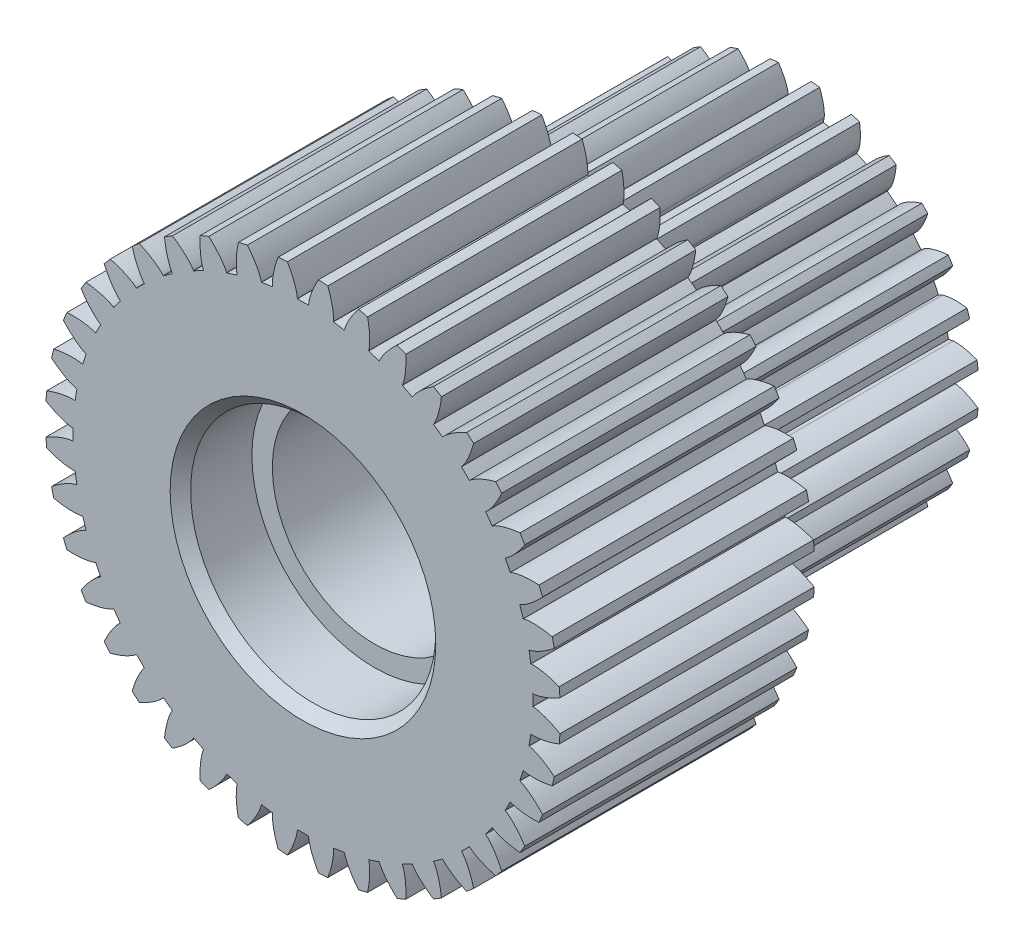
SolidWorks part; units mm, degrees
material "PLA"
ref_plane "Front Plane" through (0, 0, 0) normal (0, 0, 1) x (1, 0, 0)
ref_plane "Top Plane" through (0, 0, 0) normal (0, 1, 0) x (1, 0, 0)
ref_plane "Right Plane" through (0, 0, 0) normal (1, 0, 0) x (0, 0, -1)
sketch "Sketch1" plane through (0, 0, 0) normal (0, 0, 1) x (1, 0, 0)
  circle A0 centre (0, 0) radius 12.6
  dimension "D1" = 25.2
extrude "Boss-Extrude1" add sketch "Sketch1" along normal mid plane 12.446
sketch "Sketch2" plane through (0, 0, 0) normal (0, 0, 1) x (1, 0, 0)
  line L0 (0, 0) -> (11.9964, 0.2924) construction
  line L1 (0, 0) -> (12, 0) construction
  line L2 (0, 0) -> (11.9964, -0.2924) construction
  line L3 (11.2705, -0.2747) -> (11.2467, -0.2741)
  line L4 (11.273, 0.2747) -> (11.2467, 0.2741)
  circle A0 centre (0, 0) radius 12 construction
  circle A1 centre (0, 0) radius 11.2763 construction
  circle A2 centre (0, 0) radius 11.25
  circle A3 centre (0, 0) radius 12.6 construction
  circle A4 centre (0, 0) radius 12.6
  spline S0 degree 4 poles (11.273, 0.2747) (11.2768, 0.2749) (11.2876, 0.2755) (11.308, 0.2773) (11.3412, 0.2811) (11.3834, 0.2875) (11.4377, 0.2974) (11.5015, 0.311) (11.5713, 0.3282) (11.6468, 0.3492) (11.7218, 0.3723) (11.7963, 0.3972) (11.8701, 0.4237) (11.9591, 0.4578) (12.0652, 0.5015) (12.1882, 0.5566) (12.3264, 0.6239) (12.4657, 0.6975) (12.6016, 0.774) (12.7374, 0.8561) (12.8676, 0.9388) (13.0012, 1.0294) (13.1236, 1.1155) (13.2588, 1.2171) (13.3673, 1.3006) (13.5081, 1.4161) (13.5906, 1.486) (13.6863, 1.5697) (13.7283, 1.6078) (13.7543, 1.6313) knots 0 0 0 0 0 0.005377 0.015084 0.028532 0.04661 0.064855 0.092111 0.119476 0.146842 0.174209 0.201575 0.228941 0.256307 0.307035 0.361767 0.4165 0.471232 0.525964 0.580697 0.635429 0.690161 0.744894 0.799626 0.854358 0.909091 0.954545 1 1 1 1 1 construction
  spline S1 degree 4 poles (11.273, 0.2747) (11.2768, 0.2749) (11.2876, 0.2755) (11.308, 0.2773) (11.3412, 0.2811) (11.3834, 0.2875) (11.4377, 0.2974) (11.5015, 0.311) (11.5713, 0.3282) (11.6468, 0.3492) (11.7218, 0.3723) (11.7963, 0.3972) (11.8701, 0.4237) (11.9591, 0.4578) (12.0652, 0.5015) (12.1882, 0.5566) (12.3264, 0.6239) (12.4657, 0.6975) (12.6016, 0.774) (12.7374, 0.8561) (12.8676, 0.9388) (13.0012, 1.0294) (13.1236, 1.1155) (13.2588, 1.2171) (13.3673, 1.3006) (13.4776, 1.3911) (13.531, 1.4358) (13.5582, 1.4589) knots 0 0 0 0 0 0.005377 0.015084 0.028532 0.04661 0.064855 0.092111 0.119476 0.146842 0.174209 0.201575 0.228941 0.256307 0.307035 0.361767 0.4165 0.471232 0.525964 0.580697 0.635429 0.690161 0.744894 0.799626 0.854358 0.909091 0.909091 0.909091 0.909091 0.909091
  spline S2 degree 4 poles (11.2705, -0.2747) (11.2744, -0.2748) (11.2852, -0.2754) (11.3055, -0.2772) (11.3387, -0.2811) (11.3809, -0.2875) (11.4353, -0.2973) (11.499, -0.311) (11.5688, -0.3282) (11.6444, -0.3492) (11.7194, -0.3722) (11.7938, -0.3971) (11.8677, -0.4236) (11.9567, -0.4577) (12.0627, -0.5014) (12.1857, -0.5566) (12.3239, -0.6238) (12.4633, -0.6974) (12.5992, -0.774) (12.7349, -0.856) (12.8652, -0.9387) (12.9988, -1.0293) (13.1212, -1.1154) (13.2563, -1.217) (13.3648, -1.3005) (13.5056, -1.4161) (13.5881, -1.486) (13.6838, -1.5696) (13.7259, -1.6077) (13.7518, -1.6312) knots 0 0 0 0 0 0.005377 0.015084 0.028532 0.04661 0.064855 0.092111 0.119476 0.146842 0.174209 0.201575 0.228941 0.256307 0.307035 0.361767 0.4165 0.471232 0.525964 0.580697 0.635429 0.690161 0.744894 0.799626 0.854358 0.909091 0.954545 1 1 1 1 1 construction
  spline S3 degree 4 poles (11.2705, -0.2747) (11.2744, -0.2748) (11.2852, -0.2754) (11.3055, -0.2772) (11.3387, -0.2811) (11.3809, -0.2875) (11.4353, -0.2973) (11.499, -0.311) (11.5688, -0.3282) (11.6444, -0.3492) (11.7194, -0.3722) (11.7938, -0.3971) (11.8677, -0.4236) (11.9567, -0.4577) (12.0627, -0.5014) (12.1857, -0.5566) (12.3239, -0.6238) (12.4633, -0.6974) (12.5992, -0.774) (12.7349, -0.856) (12.8652, -0.9387) (12.9988, -1.0293) (13.1212, -1.1154) (13.2563, -1.217) (13.3648, -1.3005) (13.4751, -1.391) (13.5285, -1.4357) (13.5557, -1.4588) knots 0 0 0 0 0 0.005377 0.015084 0.028532 0.04661 0.064855 0.092111 0.119476 0.146842 0.174209 0.201575 0.228941 0.256307 0.307035 0.361767 0.4165 0.471232 0.525964 0.580697 0.635429 0.690161 0.744894 0.799626 0.854358 0.909091 0.909091 0.909091 0.909091 0.909091
  dimension "D1" = 24
  dimension "D2" = 22.5526
  dimension "D3" = 22.5
  dimension "D4" = 1.396
  dimension "D5" = 1.396
extrude "Cut-Extrude1" cut sketch "Sketch2" against normal through all both and the other way through all
pattern_circular "CirPattern2" count 40 over 360 about axis through (0, 0, 6.223) along (0, 0, -1) of "Cut-Extrude1"
sketch "Sketch3" plane through (0, 0, 6.223) normal (0, 0, 1) x (1, 0, 0)
  circle A0 centre (0, 0) radius 5
  dimension "D1" = 10
sketch "Sketch4" plane through (0, 0, -6.223) normal (0, 0, -1) x (-1, 0, 0)
  circle A0 centre (0, 0) radius 9
  dimension "D1" = 18
extrude "Boss-Extrude2" add sketch "Sketch4" along normal blind 11.6295
sketch "Sketch5" plane through (0, 0, -17.8525) normal (0, 0, -1) x (-1, 0, 0)
  line L0 (0, 0) -> (9, 0) construction
  line L1 (0, 0) -> (8.9924, 0.3707) construction
  line L2 (0, 0) -> (8.9924, -0.3707) construction
  line L3 (7.8649, 0.3242) -> (7.6435, 0.3151)
  line L4 (7.8649, -0.3242) -> (7.6435, -0.3151)
  circle A0 centre (0, 0) radius 7.8934 construction
  circle A1 centre (0, 0) radius 7.65
  arc A2 (8.9642, -0.8024) -> (8.9642, 0.8024) centre (0, 0) ccw
  spline S0 degree 4 poles (7.8649, 0.3242) (7.8676, 0.3243) (7.8752, 0.3249) (7.8984, 0.3273) (7.9441, 0.3343) (8.0002, 0.3461) (8.0643, 0.3625) (8.1257, 0.3807) (8.1779, 0.3978) (8.2297, 0.416) (8.2811, 0.4355) (8.343, 0.4604) (8.4167, 0.4922) (8.5021, 0.5323) (8.5981, 0.581) (8.6947, 0.6341) (8.789, 0.6893) (8.883, 0.7483) (8.9732, 0.8077) (9.0656, 0.8727) (9.1503, 0.9344) (9.2437, 1.0071) (9.3186, 1.0668) (9.4158, 1.1494) (9.4727, 1.1993) (9.5387, 1.259) (9.5677, 1.2861) (9.5856, 1.3028) knots 0 0 0 0 0 0.005377 0.015084 0.04661 0.092111 0.119476 0.146842 0.174209 0.201575 0.228941 0.256307 0.307035 0.361767 0.4165 0.471232 0.525964 0.580697 0.635429 0.690161 0.744894 0.799626 0.854358 0.909091 0.954545 1 1 1 1 1 construction
  spline S1 degree 4 poles (7.8649, 0.3242) (7.8676, 0.3243) (7.8752, 0.3249) (7.8984, 0.3273) (7.9441, 0.3343) (8.0002, 0.3461) (8.0643, 0.3625) (8.1257, 0.3807) (8.1779, 0.3978) (8.2297, 0.416) (8.2811, 0.4355) (8.343, 0.4604) (8.4167, 0.4922) (8.5021, 0.5323) (8.5981, 0.581) (8.6947, 0.6341) (8.789, 0.6893) (8.883, 0.7483) (8.9732, 0.8077) (9.0656, 0.8727) (9.1503, 0.9344) (9.2437, 1.0071) (9.3186, 1.0668) (9.3948, 1.1315) (9.4316, 1.1634) (9.4504, 1.1799) knots 0 0 0 0 0 0.005377 0.015084 0.04661 0.092111 0.119476 0.146842 0.174209 0.201575 0.228941 0.256307 0.307035 0.361767 0.4165 0.471232 0.525964 0.580697 0.635429 0.690161 0.744894 0.799626 0.854358 0.909091 0.909091 0.909091 0.909091 0.909091
  spline S2 degree 4 poles (7.8649, -0.3242) (7.8676, -0.3243) (7.8752, -0.3249) (7.8984, -0.3273) (7.9441, -0.3343) (8.0002, -0.3461) (8.0643, -0.3625) (8.1257, -0.3807) (8.1779, -0.3978) (8.2297, -0.416) (8.2811, -0.4355) (8.343, -0.4604) (8.4167, -0.4922) (8.5021, -0.5323) (8.5981, -0.581) (8.6947, -0.6341) (8.789, -0.6893) (8.883, -0.7483) (8.9732, -0.8077) (9.0656, -0.8727) (9.1503, -0.9344) (9.2437, -1.0071) (9.3186, -1.0668) (9.4158, -1.1494) (9.4727, -1.1993) (9.5387, -1.259) (9.5677, -1.2861) (9.5856, -1.3028) knots 0 0 0 0 0 0.005377 0.015084 0.04661 0.092111 0.119476 0.146842 0.174209 0.201575 0.228941 0.256307 0.307035 0.361767 0.4165 0.471232 0.525964 0.580697 0.635429 0.690161 0.744894 0.799626 0.854358 0.909091 0.954545 1 1 1 1 1 construction
  spline S3 degree 4 poles (7.8649, -0.3242) (7.8676, -0.3243) (7.8752, -0.3249) (7.8984, -0.3273) (7.9441, -0.3343) (8.0002, -0.3461) (8.0643, -0.3625) (8.1257, -0.3807) (8.1779, -0.3978) (8.2297, -0.416) (8.2811, -0.4355) (8.343, -0.4604) (8.4167, -0.4922) (8.5021, -0.5323) (8.5981, -0.581) (8.6947, -0.6341) (8.789, -0.6893) (8.883, -0.7483) (8.9732, -0.8077) (9.0656, -0.8727) (9.1503, -0.9344) (9.2437, -1.0071) (9.3186, -1.0668) (9.3948, -1.1315) (9.4316, -1.1634) (9.4504, -1.1799) knots 0 0 0 0 0 0.005377 0.015084 0.04661 0.092111 0.119476 0.146842 0.174209 0.201575 0.228941 0.256307 0.307035 0.361767 0.4165 0.471232 0.525964 0.580697 0.635429 0.690161 0.744894 0.799626 0.854358 0.909091 0.909091 0.909091 0.909091 0.909091
  dimension "D2" = 15.3
  dimension "D3" = 18
  dimension "D1" = 15.7868
  dimension "D4" = 2.36
  dimension "D5" = 2.36
extrude "Cut-Extrude2" cut sketch "Sketch5" against normal up to surface (11.6295 mm away)
pattern_circular "CirPattern3" count 28 over 360 about axis through (0, 0, -17.8525) along (0, 0, 1) of "Cut-Extrude2"
extrude "Cut-Extrude3" cut sketch "Sketch3" against normal through all contours A0
sketch "Sketch7" plane through (0, 0, -17.8525) normal (0, 0, -1) x (-1, 0, 0)
  circle A0 centre (0, 0) radius 6
  dimension "D1" = 12
extrude "Cut-Extrude4" cut sketch "Sketch7" against normal blind 3.5
ref_plane "Plane1" through (0, 0, -5.8148) normal (0, 0, -1) x (-1, 0, 0)
mirror "Mirror1" about plane through (0, 0, -5.8148) normal (0, 0, -1) of "Cut-Extrude4"
chamfer "Chamfer1" distance 0.5 angle 45 2 edges at (-6, 0, 6.223) (-6, 0, -17.8525)
equation "\"module\" = 0.6"
equation "\"pressure angle\" = 20.0"
equation "\"h_a\" = 0.6"
equation "\"h_b\" = 0.75"
equation "\"clr_tip_root\" = 0.15000000000000002"
equation "\"D1@Sketch1\" = \"dp_p_b\" + 2 * \"h_a\""
equation "\"D1@Boss-Extrude1\" = \"fw_p_b\""
equation "\"D1@Sketch2\" = \"dp_p_b\""
equation "\"D2@Sketch2\"= \"db_p_b\""
equation "\"D3@Sketch2\" = \"dp_p_b\" - 2 * \"h_b\""
equation "\"Nr_s\" = 116"
equation "\"pressure_angle\" = 20.0"
equation "\"h_f\" = 0.75"
equation "\"dp_r_s\" = 69.6"
equation "\"bearing_ID\" = 65"
equation "\"bearing_OD\" = 85"
equation "\"bearing_height\" = 10"
equation "\"clearance_planet\" = 1.5"
equation "\"case_dist\" = 6.5"
equation "\"Motor_case_OD_max\" = 115.5"
equation "\"case_mounting_PCD\" = 108.0"
equation "\"bearing mount thickness\" = 8"
equation "\"case_mounting_hole_dia\" = 3"
equation "\"output_mounting_PCD\" = 93"
equation "\"output_mounting_hole_dia\" = 4"
equation "\"clearance_case_mount_holes_shell_thickness\" = 1"
equation "\"motor_case_OD_base\" = 106.0"
equation "\"sec_carrier_thickness\" = 5"
equation "\"sun_coupler_hub_thickness\" = 4"
equation "\"clearance_sun_coupler_sec_carrier\" = 1.5"
equation "\"clearance_motor_and_case\" = 14.5"
equation "\"motor_OD\" = 72"
equation "\"Motor_case_thickness\" = 2.5"
equation "\"Motor_case_ID\" = 101.0"
equation "\"case_mounting_hole_shift\" = 1.0"
equation "\"output_mounting_nut_wrench_size\" = 7"
equation "\"output_mounting_nut_thickness\" = 3.2"
equation "\"case_mounting_hole_allen_socket_dia\" = 5.5"
equation "\"output_mounting_nut_depth\" = 3"
equation "\"case_mounting_bolt_depth\" = 4.5"
equation "\"Ns\" = 48"
equation "\"ring_radial_thickness\" = 5"
equation "\"ring_to_chamfer_clearance\" = 1.5"
equation "\"Motor_case_OD_base_to_chamfer\" = 5"
equation "\"pattern_offset_from_motor_case_OD_base\" = 3"
equation "\"pattern_bulge_dia\" = 3"
equation "\"pattern_num_bulge\" = 18"
equation "\"pattern_depth\" = 2"
equation "\"motor_height\" = 27"
equation "\"case_mounting_wrench_size\" = 5.5"
equation "\"case_mounting_nut_clearance\" = 2"
equation "\"base_plate_thickness\" = 4"
equation "\"case_mounting_nut_thickness\" = 2.4"
equation "\"case_mounting_surface_height\" = 4"
equation "\"motor_mount_hole_PCD\" = 32"
equation "\"motor_mount_hole_dia\" = 4"
equation "\"motor_mount_hole_num\" = 4"
equation "\"central_hole_offset_from_motor_mount_PCD\" = 5"
equation "\"wire_slot_dist_from_center\" = 26"
equation "\"wire_slot_length\" = 10"
equation "\"wire_slot_radius\" = 2.5"
equation "\"driver_upper_holes_dist_from_center\" = 29"
equation "\"driver_lower_holes_dist_from_center\" = 13"
equation "\"driver_side_holes_dist_from_center\" = 22.5"
equation "\"driver_mount_holes_dia\" = 3"
equation "\"driver_mount_inserts_OD\" = 4.8"
equation "\"driver_mount_thickness\" = 1.5"
equation "\"driver_mount_height\" = 6"
equation "\"air_flow_hole_offset\" = 3"
equation "\"num_planet\" = 4"
equation "\"planet_pin_bolt_dia\" = 5"
equation "\"planet_pin_socket_head_dia\" = 8.5"
equation "\"carrier_PCD\" = 52.8"
equation "\"planet_shaft_dia\" = 8"
equation "\"planet_shaft_step_offset\" = 1"
equation "\"carrier_trapezoidal_support_sun_offset\" = 5"
equation "\"carrier_trapezoidal_support_hole_PCD_offset_bearing_ID\" = 4"
equation "\"carrier_trapezoidal_support_hole_dia\" = 3"
equation "\"carrier_trapezoidal_support_hole_socket_head_dia\" = 5.5"
equation "\"carrier_bearing_step_width\" = 1.5"
equation "\"standard_clearance_1_5mm\" = 1.5"
equation "\"standard_fillet_1_5mm\" = 1.5"
equation "\"sun_shaft_bearing_OD\" = 16"
equation "\"sun_shaft_bearing_width\" = 5"
equation "\"standard_bearing_insertion_chamfer\" = 0.5"
equation "\"carrier_trapezoidal_support_hole_wrench_size\" = 5.5"
equation "\"planet_pin_bolt_wrench_size\" = 8"
equation "\"planet_bearing_OD\" = 12"
equation "\"planet_bearing_width\" = 3.5"
equation "\"planet_bore\" = 10"
equation "\"D1@Sketch3\"=\"planet_bore\""
equation "\"Np_b\" = 40"
equation "\"dp_s\" = 28.799999999999997"
equation "\"db_s\" = 27.06314747863416"
equation "\"fw_s_calc\" = 2.359230083666351"
equation "\"alpha_s\" = 0.8539582918412343"
equation "\"beta_s\" = 2.0420834163175314"
equation "\"dp_p_b\" = 24.0"
equation "\"db_p_b\" = 22.552622898861802"
equation "\"fw_p_s\" = 11.6295029769434"
equation "\"alpha_p_b\" = 0.8539582918412414"
equation "\"beta_p_b\" = 2.792083416317517"
equation "\"motor_output_hole_PCD\" = 22"
equation "\"motor_output_hole_dia\" = 3"
equation "\"motor_output_hole_num\" = 4"
equation "\"sun_shaft_bearing_ID\" = 8"
equation "\"sun_hub_dia\" = 28.0"
equation "\"sun_central_bolt_dia\" = 5"
equation "\"sun_central_bolt_socket_head_dia\" = 8.5"
equation "\"fw_s_used\" = 31.575468444261382"
equation "\"motor_output_hole_CSK_OD\" = 6"
equation "\"motor_output_hole_CSK_head_height\" = 1.5"
equation "\"bearing_retainer_thickness\" = 2"
equation "\"Np_s\" = 28"
equation "\"fw_p_b\" = 12.445965467317981"
equation "\"dp_p_s\" = 16.8"
equation "\"db_p_s\" = 15.786836029203263"
equation "\"alpha_p_s\" = 0.8539582918412343"
equation "\"beta_p_s\" = 4.72065484488896"
equation "\"D1@Sketch4\"=\"dp_p_s\" + 2 * \"h_a\""
equation "\"D1@Boss-Extrude2\"=\"fw_p_s\""
equation "\"D2@Sketch5\"=\"dp_p_s\" - 2 * \"h_b\""
equation "\"D3@Sketch5\"=\"dp_p_s\"+2 * \"h_a\" "
equation "\"D1@Sketch5\"=\"db_p_s\""
equation "\"D1@CirPattern3\"=\"Np_s\""
equation "\"D4@Sketch5\"=\"beta_p_s\"/2"
equation "\"D5@Sketch5\"=\"beta_p_s\"/2"
equation "\"D4@Sketch2\"=\"beta_p_b\"/2"
equation "\"D5@Sketch2\"=\"beta_p_b\"/2"
equation "\"D1@Sketch7\"=\"planet_bearing_OD\""
equation "\"D1@Cut-Extrude4\"=\"planet_bearing_width\""
equation "\"D1@Chamfer1\"=\"standard_bearing_insertion_chamfer\""
equation "\"D1@CirPattern2\"=\"Np_b\""
equation "\"Nr_b\" = 128"
equation "\"dp_r_b\" = 76.8"
equation "\"db_r_b\" = 72.16839327635776"
equation "\"fw_r_b\" = 12.445965467317981"
equation "\"alpha_r_b\" = 0.8539582918412556"
equation "\"beta_r_b\" = 3.114166583682511"
equation "\"ring_OD_b\" = 86.8"
equation "\"Fillet10\"= IIF ( \"ring_OD_b\" > ( \"bearing_OD\" + 2 * \"bearing mount thickness\" ) , \"suppressed\" , \"unsuppressed\" )"
equation "\"Fillet11\"= IIF ( \"ring_OD_b\" < ( \"bearing_OD\" + 2 * \"bearing mount thickness\" ) , \"suppressed\" , \"unsuppressed\" )"
equation "\"clr_tip_root_s\" = 0.15000000000000002"
equation "\"db_r_s\" = 65.40260640669922"
equation "\"fw_r_s\" = 10.1295029769434"
equation "\"alpha_r_s\" = 0.8539582918412343"
equation "\"beta_r_s\" = 3.2596407216135033"
equation "\"small_ring_case_thickness\" = 4"
equation "\"carrier_thickness\" = 4"
equation "\"small_ring_output_wall_thickness\" = 5"
equation "\"small_ring_output_wall_to_bearing_shaft_attachement_hole_dia\" = 4"
equation "\"small_ring_output_wall_to_bearing_shaft_attachement_hole_depth\" = 6.5"
equation "\"small_ring_output_wall_to_bearing_shaft_attachement_nut_wrench\" = 7"
equation "\"small_ring_output_wall_to_bearing_shaft_attachement_nut_thickness\" = 3.2"
equation "\"small_ring_output_wall_to_bearing_shaft_attachement_hole_pcd\" = 12"
equation "\"small_ring_output_wall_to_bearing_shaft_attachement_hole_num\" = 3"
equation "\"small_ring_output_wall_to_bearing_shaft_attachement_hole_CSK_OD\" = 8"
equation "\"small_ring_output_wall_to_bearing_shaft_attachement_hole_CSK_head_height\" = 2.0"
equation "\"carrier_small_ring_inner_bearing_ID\" = 20"
equation "\"carrier_small_ring_inner_bearing_OD\" = 32"
equation "\"carrier_small_ring_inner_bearing_height\" = 7"
equation "\"carrier_small_ring_inner_bearing_flap\" = 2"
equation "\"gear_casing_big_ring_to_bearing_dist\" = 20.6295029769434"
equation "\"gear_casing_thickness\" = 4"
